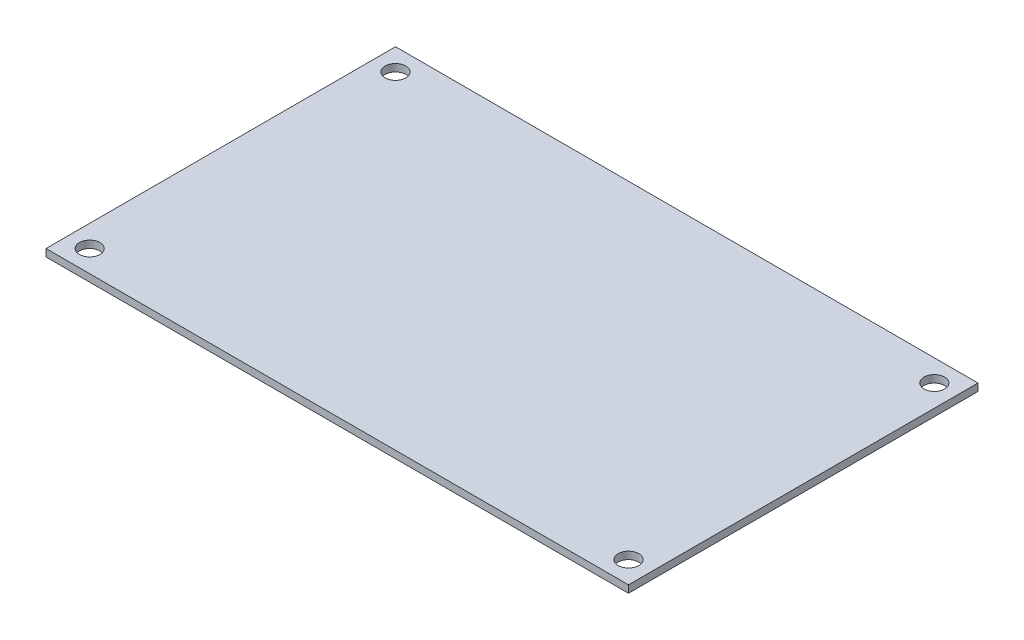
SolidWorks part; units mm, degrees
ref_plane "Front" through (0, 0, 0) normal (0, 0, 1) x (1, 0, 0)
ref_plane "Top" through (0, 0, 0) normal (0, 1, 0) x (1, 0, 0)
ref_plane "Right" through (0, 0, 0) normal (1, 0, 0) x (0, 0, -1)
sketch "Sketch1" plane through (0, 0, 0) normal (0, 1, 0) x (1, 0, 0)
  line L1 (-63.5, -38.1) -> (63.5, -38.1)
  line L2 (-63.5, -38.1) -> (-63.5, 38.1)
  line L3 (-63.5, 38.1) -> (63.5, 38.1)
  line L4 (63.5, -38.1) -> (63.5, 38.1)
  line L5 (-63.5, -38.1) -> (63.5, 38.1) construction
  line L6 (-63.5, 38.1) -> (63.5, -38.1) construction
  point P0 (0, 0)
  dimension "D1" = 127
  dimension "D2" = 76.2
extrude "Boss-Extrude1" add sketch "Sketch1" along normal blind 1.6
hole_wizard "M4 Clearance Hole1" positions "Sketch2" profile "Sketch3" hole size "M4" standard "ANSI Metric"
sketch "Sketch2" plane through (0, 1.6, 0) normal (0, 1, 0) x (1, 0, 0)
  line L1 (-58.7375, -33.3375) -> (58.7375, -33.3375)
  line L2 (-58.7375, -33.3375) -> (-58.7375, 33.3375)
  line L3 (-58.7375, 33.3375) -> (58.7375, 33.3375)
  line L4 (58.7375, -33.3375) -> (58.7375, 33.3375)
  line L5 (-58.7375, -33.3375) -> (58.7375, 33.3375) construction
  line L6 (-58.7375, 33.3375) -> (58.7375, -33.3375) construction
  line L7 (63.5, -38.1) -> (63.5, 38.1) construction
  line L8 (63.5, 38.1) -> (-63.5, 38.1) construction
  point P0 (-58.7375, 33.3375)
  point P2 (-58.7375, -33.3375)
  point P4 (58.7375, -33.3375)
  point P6 (58.7375, 33.3375)
  point P122 (0, 0)
  point P124 (0, 0)
  point P125 (0, 0)
  point P126 (0, 0)
  point P127 (0, 0)
  point P128 (0, 0)
  point P129 (0, 0)
  point P132 (63.5, 0)
  dimension "D1" = 4.7625
  dimension "D2" = 4.7625
sketch "Sketch3" plane through (-58.7375, 1.6, -33.3375) normal (1, 0, 0) x (0, 0, 1)
  line L0 (0, 0) -> (0, 51.3519)
  line L1 (0, 51.3519) -> (2.25, 50)
  line L2 (2.25, 50) -> (2.25, 0)
  line L5 (2.25, 0) -> (0, 0)
  line L10 (0, 51.3519) -> (-2.25, 50) construction
  line L11 (0, -6.35) -> (0, 107.95) construction
  dimension "Hole Dia." = 4.5
  dimension "Hole Depth" = 50
  dimension "Drill Angle" = 118
